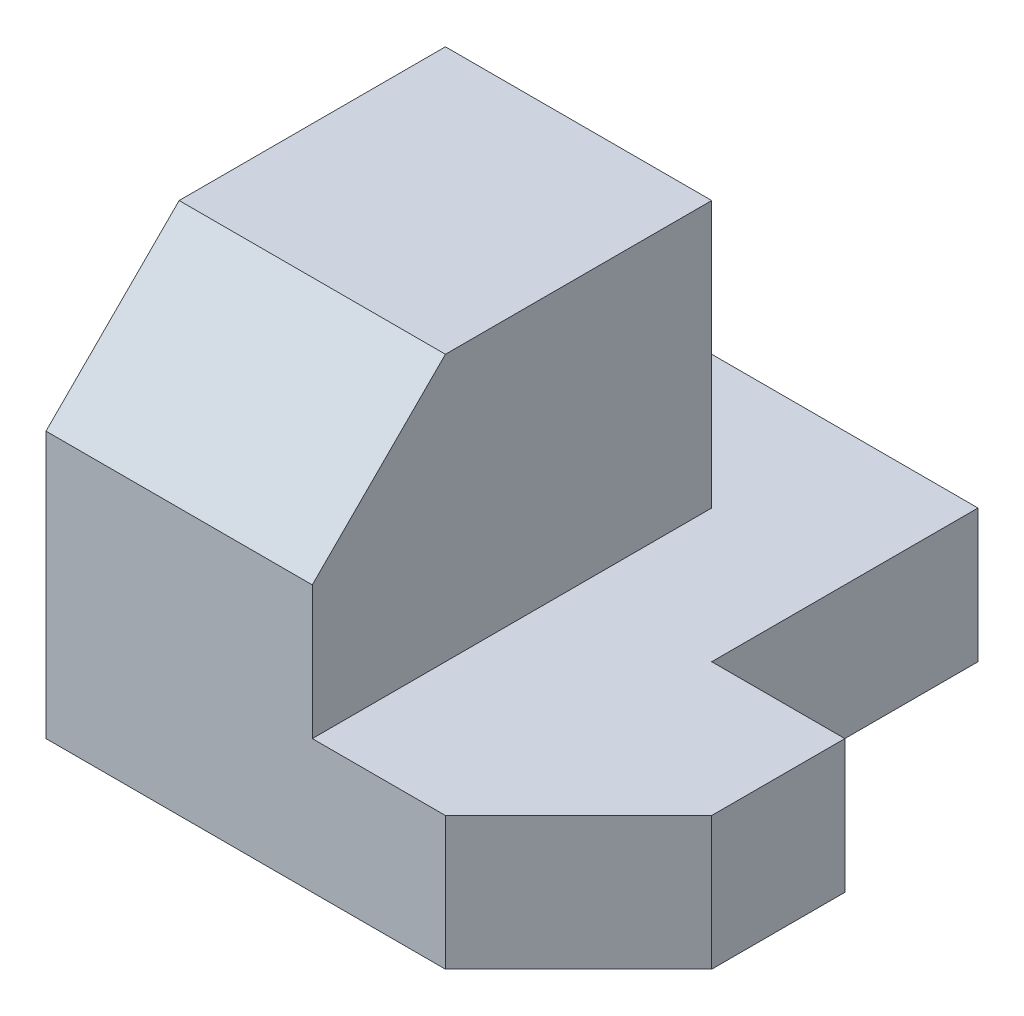
SolidWorks part; units mm, degrees
ref_plane "前基準面" through (0, 0, 0) normal (0, 0, 1) x (1, 0, 0)
ref_plane "上基準面" through (0, 0, 0) normal (0, 1, 0) x (1, 0, 0)
ref_plane "右基準面" through (0, 0, 0) normal (1, 0, 0) x (0, 0, -1)
sketch "草圖1" plane through (0, 0, 0) normal (0, 1, 0) x (1, 0, 0)
  line L0 (0, 0) -> (0, 21.6237) construction
  line L1 (0, 0) -> (0, 20)
  line L2 (0, 20) -> (15, 20)
  line L3 (15, 20) -> (15, 10)
  line L4 (15, 10) -> (20, 10)
  line L5 (20, 10) -> (20, 5)
  line L6 (20, 5) -> (15, 0)
  line L7 (15, 0) -> (0, 0)
  line L8 (0, 15) -> (10, 15)
  line L9 (10, 15) -> (10, 0)
  line L10 (10, 0) -> (10, 5)
  line L11 (10, 5) -> (0, 5)
  point P10 (17.5, 10)
  dimension "D1" = 20
  dimension "D2" = 15
  dimension "D3" = 20
  dimension "D4" = 5
  dimension "D5" = 10
  dimension "D6" = 15
  dimension "D7" = 15
  dimension "D8" = 10
  dimension "D9" = 5
extrude "填料-伸長1" add sketch "草圖1" along normal blind 5 contours L8 L9 L7 L6 L5 L4 L3 L2 L1 | L11 L9 L8 L1 | L9 L11 L1 L7 region at (5, 0, -2.5) region at (5, 0, -10) region at (11.4444, 0, -11.2222)
extrude "填料-伸長2" add sketch "草圖1<3>" along normal blind 15 contours L11 L9 L8 L1 | L9 L11 L1 L7 region at (5, 0, -2.5) region at (5, 0, -10)
sketch "草圖1<3>" plane through (0, 0, 0) normal (0, 1, 0) x (1, 0, 0) same geometry as "草圖1"
sketch "草圖2" plane through (10, 0, 0) normal (1, 0, 0) x (0, 0, -1)
  line L0 (0, 15) -> (0, 10)
  line L1 (0, 15) -> (0, 5) construction
  line L2 (0, 10) -> (5, 15)
  line L3 (15, 15) -> (0, 15) construction
  line L4 (5, 15) -> (0, 15)
  dimension "D1" = 5
  dimension "D2" = 5
extrude "除料-伸長1" cut sketch "草圖2" against normal blind 15
